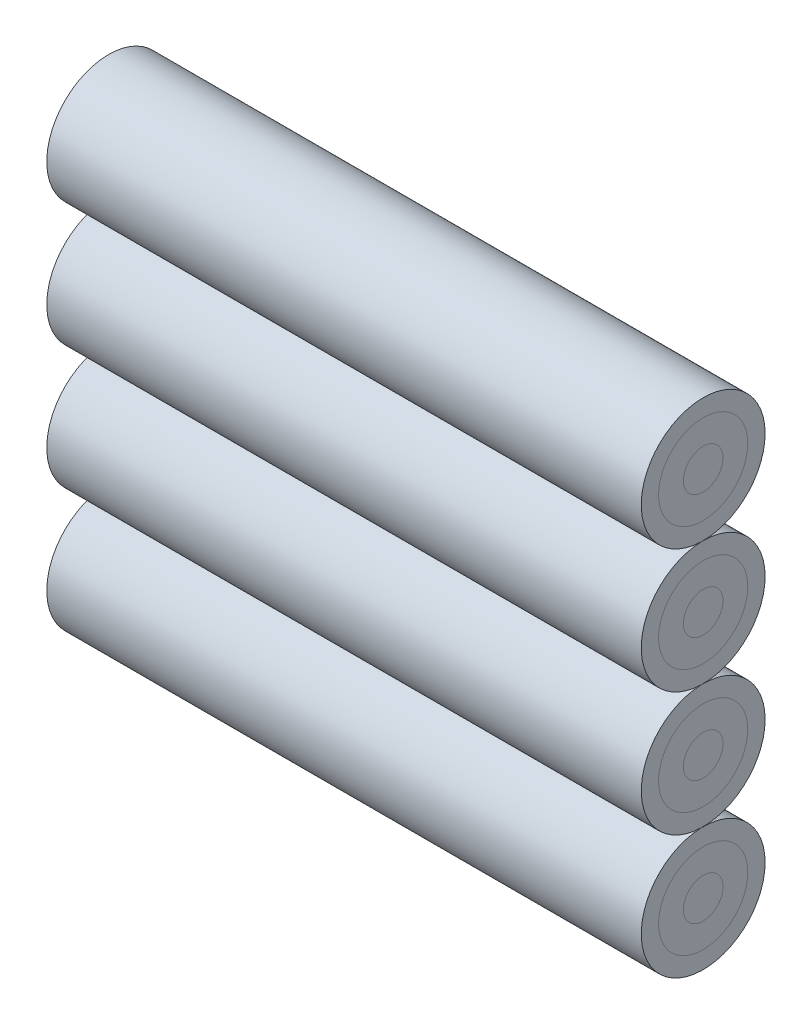
SolidWorks part; units mm, degrees
ref_plane "前视基准面" through (0, 0, 0) normal (0, 0, 1) x (1, 0, 0)
ref_plane "上视基准面" through (0, 0, 0) normal (0, 1, 0) x (1, 0, 0)
ref_plane "右视基准面" through (0, 0, 0) normal (1, 0, 0) x (0, 0, -1)
sketch "草图1" plane through (0, 0, 0) normal (1, 0, 0) x (0, 0, -1)
  circle A0 centre (0, 375) radius 125
  circle A1 centre (0, 125) radius 125
  circle A2 centre (0, -125) radius 125
  circle A3 centre (0, -375) radius 125
extrude "凸台-拉伸1" add sketch "草图1" along normal blind 1200 contours A3 | A0 | A1 | A2 region at (0, -375, 0)
sketch "草图2" plane through (1200, 0, 0) normal (1, 0, 0) x (0, 0, -1)
  circle A0 centre (0, 375) radius 90
  circle A1 centre (0, 125) radius 90
  circle A2 centre (0, -125) radius 90
  circle A3 centre (0, -375) radius 90
extrude "切除-拉伸1" cut sketch "草图2" against normal through all
sketch "草图3" plane through (0, 0, 0) normal (1, 0, 0) x (0, 0, -1)
  circle A0 centre (0, 375) radius 90
  circle A1 centre (0, 125) radius 90
  circle A2 centre (0, -125) radius 90
  circle A3 centre (0, -375) radius 90
extrude "凸台-拉伸3" add sketch "草图3" along normal blind 1200 separate body
sketch "草图4" plane through (1200, 0, 0) normal (1, 0, 0) x (0, 0, -1)
  circle A0 centre (0, 375) radius 40
  circle A1 centre (0, 125) radius 40
  circle A2 centre (0, -125) radius 40
  circle A3 centre (0, -375) radius 40
extrude "切除-拉伸2" cut sketch "草图4" against normal through all
sketch "草图5" plane through (0, 0, 0) normal (1, 0, 0) x (0, 0, -1)
  circle A0 centre (0, 375) radius 40
  circle A1 centre (0, 125) radius 40
  circle A2 centre (0, -125) radius 40
  circle A3 centre (0, -375) radius 40
extrude "凸台-拉伸7" add sketch "草图5" along normal blind 1200 separate body
